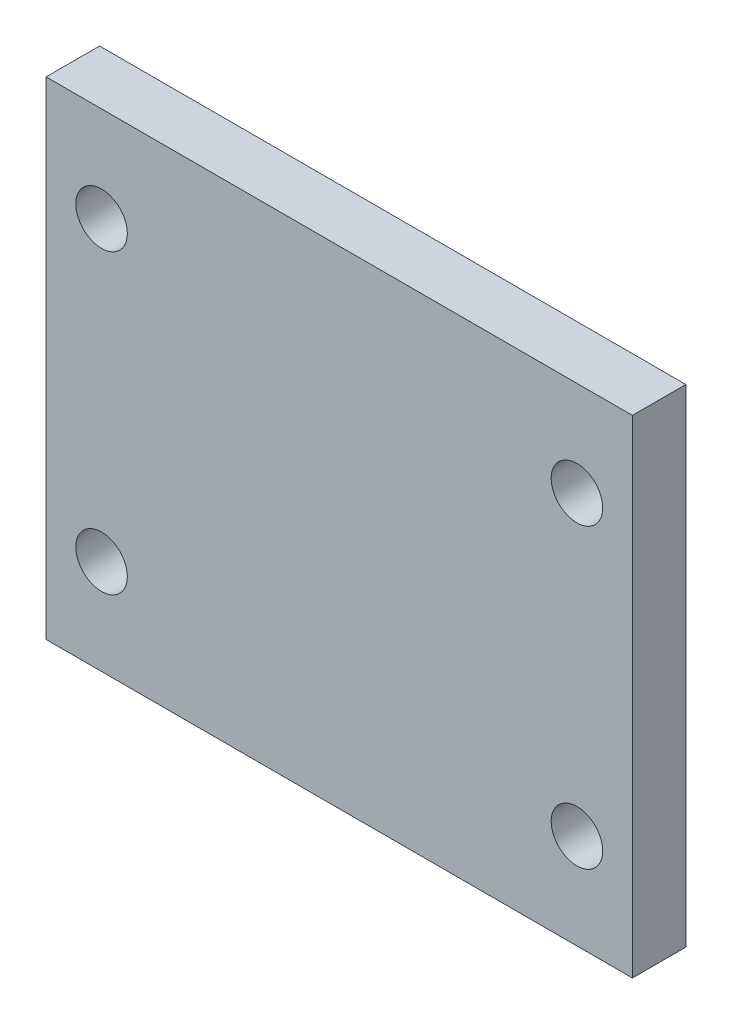
SolidWorks part; units mm, degrees
ref_plane "Front Plane" through (0, 0, 0) normal (0, 0, 1) x (1, 0, 0)
ref_plane "Top Plane" through (0, 0, 0) normal (0, 1, 0) x (1, 0, 0)
ref_plane "Right Plane" through (0, 0, 0) normal (1, 0, 0) x (0, 0, -1)
sketch "Sketch1" plane through (0, 0, 0) normal (0, 0, 1) x (1, 0, 0)
  line L1 (148, -123) -> (-148, -123)
  line L2 (148, -123) -> (148, 123)
  line L3 (148, 123) -> (-148, 123)
  line L4 (-148, -123) -> (-148, 123)
  line L5 (148, -123) -> (-148, 123) construction
  line L6 (148, 123) -> (-148, -123) construction
  circle A0 centre (120, -75) radius 13 construction
  circle A1 centre (-120, -75) radius 13 construction
  circle A2 centre (-120, 75) radius 13 construction
  circle A3 centre (120, 75) radius 13 construction
  circle A4 centre (-120, 75) radius 13
  circle A5 centre (120, 75) radius 13
  circle A6 centre (120, -75) radius 13
  circle A7 centre (-120, -75) radius 13
  point P0 (0, 0)
  dimension "D1" = 296
  dimension "D2" = 246
extrude "Extrude1" add sketch "Sketch1" along normal blind 27
